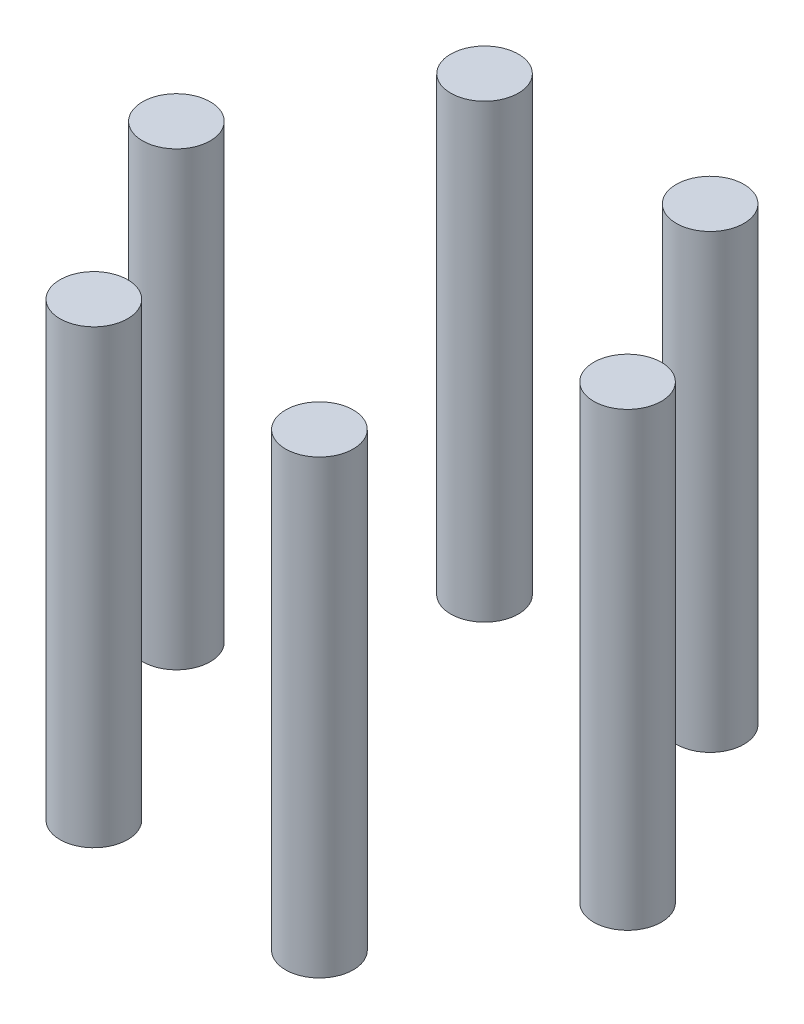
SolidWorks part; units mm, degrees
ref_plane "Front Plane" through (0, 0, 0) normal (0, 0, 1) x (1, 0, 0)
ref_plane "Top Plane" through (0, 0, 0) normal (0, 1, 0) x (1, 0, 0)
ref_plane "Right Plane" through (0, 0, 0) normal (1, 0, 0) x (0, 0, -1)
sketch "Sketch1" plane through (0, 0, 0) normal (0, 1, 0) x (1, 0, 0)
  line L0 (-15.4, 0) -> (14.4, 0) construction
  line L1 (0, 0) -> (0, 14.9128) construction
  line L2 (0, 0) -> (0, -14.9128) construction
  line L3 (0, 0) -> (-0.5, 0) construction
  line L4 (-0.5, 0) -> (-0.5, 15.3103) construction
  line L5 (-0.5, 0) -> (-0.5, -15.3103) construction
  line L6 (14.4, 0) -> (15.5, 0) construction
  line L7 (0, 0) -> (10, 0) construction
  line L8 (7.9, 0) -> (9.5, 0)
  line L9 (-0.5, 0) -> (9.5, 0) construction
  line L10 (-0.5, 15.3103) -> (-0.5, -15.3103) construction
  circle A0 centre (-0.5, 0) radius 16
  circle A1 centre (15.5, 0) radius 1
  circle A2 centre (15.0351, -3.8291) radius 1
  circle A3 centre (13.6673, -7.4356) radius 1
  circle A4 centre (11.4762, -10.61) radius 1
  circle A5 centre (8.589, -13.1677) radius 1
  circle A6 centre (5.1737, -14.9603) radius 1
  circle A7 centre (1.4286, -15.8833) radius 1
  circle A8 centre (-2.4286, -15.8833) radius 1
  circle A9 centre (-6.1737, -14.9603) radius 1
  circle A10 centre (-9.589, -13.1677) radius 1
  circle A11 centre (-12.4762, -10.61) radius 1
  circle A12 centre (-14.6673, -7.4356) radius 1
  circle A13 centre (-16.0351, -3.8291) radius 1
  circle A14 centre (-16.5, 0) radius 1
  circle A15 centre (-16.0351, 3.8291) radius 1
  circle A16 centre (-14.6673, 7.4356) radius 1
  circle A17 centre (-12.4762, 10.61) radius 1
  circle A18 centre (-9.589, 13.1677) radius 1
  circle A19 centre (-6.1737, 14.9603) radius 1
  circle A20 centre (-2.4286, 15.8833) radius 1
  circle A21 centre (1.4286, 15.8833) radius 1
  circle A22 centre (5.1737, 14.9603) radius 1
  circle A23 centre (8.589, 13.1677) radius 1
  circle A24 centre (11.4762, 10.61) radius 1
  circle A25 centre (13.6673, 7.4356) radius 1
  circle A26 centre (15.0351, 3.8291) radius 1
  circle A27 centre (0, 0) radius 10
  circle A28 centre (10, 0) radius 2.1
  circle A29 centre (5, -8.6603) radius 2.1
  circle A30 centre (-5, -8.6603) radius 2.1
  circle A31 centre (-10, 0) radius 2.1
  circle A32 centre (-5, 8.6603) radius 2.1
  circle A33 centre (5, 8.6603) radius 2.1
  circle A34 centre (-6, 8.6603) radius 2.1
  circle A35 centre (4, 8.6603) radius 2.1
  circle A36 centre (9, 0) radius 2.1
  circle A37 centre (4, -8.6603) radius 2.1
  circle A38 centre (-6, -8.6603) radius 2.1
  circle A39 centre (-1, 0) radius 10
  circle A40 centre (-11, 0) radius 2.1
  circle A41 centre (9.5, 0) radius 1.5
  circle A42 centre (4.5, -8.6603) radius 1.5
  circle A43 centre (-5.5, -8.6603) radius 1.5
  circle A44 centre (-10.5, 0) radius 1.5
  circle A45 centre (-5.5, 8.6603) radius 1.5
  circle A46 centre (4.5, 8.6603) radius 1.5
  spline S0 degree 4 poles (14.1521, 3.1658) (14.188, 3.1199) (14.2658, 3.0332) (14.3775, 2.9384) (14.515, 2.8555) (14.6203, 2.806) (14.6874, 2.778) (14.7412, 2.7556) (14.7939, 2.7309) (14.8442, 2.7016) (14.9616, 2.6171) (15.116, 2.4418) (15.2531, 2.163) (15.3044, 1.8261) (15.2781, 1.5454) (15.2134, 1.3341) (15.1457, 1.199) (15.0717, 1.0959) (14.999, 1.0246) (14.9346, 0.9749) (14.8529, 0.9144) (14.7598, 0.8351) (14.6613, 0.7318) (14.5658, 0.5985) (14.4899, 0.4547) (14.4445, 0.3242) (14.4198, 0.2202) (14.4058, 0.1237) (14.3997, 0.036) (14.399, -0.0233) (14.4055, -0.1232) (14.4175, -0.2057) (14.4353, -0.2848) (14.4589, -0.3638) (14.4955, -0.4601) (14.5538, -0.5777) (14.629, -0.6905) (14.7205, -0.7952) (14.8099, -0.8785) (14.886, -0.9397) (14.9653, -0.9969) (15.0394, -1.0608) (15.1018, -1.1365) (15.1543, -1.2193) (15.2086, -1.3292) (15.2563, -1.4688) (15.2881, -1.6381) (15.2945, -1.881) (15.2523, -2.1199) (15.1638, -2.3444) (15.0424, -2.5231) (14.9425, -2.6287) (14.8453, -2.7036) (14.7572, -2.7504) (14.6644, -2.7867) (14.5734, -2.827) (14.4636, -2.8857) (14.309, -2.9902) (14.1305, -3.1658) (13.9721, -3.435) (13.894, -3.7733) (13.9169, -4.0803) (13.9952, -4.3102) (14.0824, -4.4685) (14.1503, -4.5677) (14.21, -4.6429) (14.2706, -4.7176) (14.3202, -4.8002) (14.3654, -4.9109) (14.3993, -5.0496) (14.4169, -5.2624) (14.3843, -5.5009) (14.3041, -5.731) (14.178, -5.9418) (14.0479, -6.0957) (13.9108, -6.2086) (13.7771, -6.2844) (13.6546, -6.3259) (13.5506, -6.3413) (13.4467, -6.3556) (13.3441, -6.3782) (13.2186, -6.4164) (13.0491, -6.4902) (12.8504, -6.6239) (12.6494, -6.8484) (12.5061, -7.1523) (12.463, -7.451) (12.49, -7.6921) (12.5392, -7.8624) (12.5803, -7.968) (12.6183, -8.0504) (12.6544, -8.1336) (12.6783, -8.2214) (12.6929, -8.336) (12.6907, -8.4762) (12.6543, -8.6855) (12.5452, -8.9512) (12.3731, -9.1837) (12.1492, -9.3663) (11.9533, -9.4633) (11.8116, -9.5062) (11.6867, -9.5225) (11.5835, -9.517) (11.4812, -9.5034) (11.3782, -9.4969) (11.2749, -9.4982) (11.1721, -9.508) (11.0085, -9.5382) (10.791, -9.6158) (10.5438, -9.7787) (10.3474, -10.0243) (10.2402, -10.2686) (10.1943, -10.4842) (10.1853, -10.6384) (10.1931, -10.7705) (10.2091, -10.8795) (10.2256, -10.9662) (10.236, -11.0539) (10.2331, -11.1423) (10.2158, -11.2534) (10.1767, -11.3842) (10.0886, -11.5718) (9.9146, -11.8006) (9.6439, -12.0158) (9.3384, -12.1314) (9.0923, -12.1519) (8.9388, -12.1247) (8.8741, -12.1049) (8.8233, -12.0863) (8.76, -12.0622) (8.6577, -12.0268) (8.5127, -11.9913) (8.2954, -11.971) (8.0233, -12.0058) (7.7397, -12.12) (7.4775, -12.3303) (7.3093, -12.5758) (7.2277, -12.7964) (7.1948, -12.9647) (7.1831, -13.0729) (7.1774, -13.16) (7.1639, -13.2682) (7.1207, -13.3961) (7.0432, -13.5357) (6.8963, -13.7154) (6.6678, -13.8963) (6.3478, -14.0387) (6.02, -14.0727) (5.7619, -14.0269) (5.5985, -13.9438) (5.5126, -13.8801) (5.4018, -13.8057) (5.2599, -13.7303) (5.0524, -13.6565) (4.7738, -13.623) (4.4626, -13.6683) (4.1888, -13.7999) (3.9912, -13.9665) (3.8578, -14.1339) (3.7826, -14.2632) (3.7309, -14.3799) (3.6959, -14.48) (3.6689, -14.5606) (3.6251, -14.6573) (3.5494, -14.7647) (3.44, -14.8752) (3.2557, -15.006) (2.9928, -15.1201) (2.6515, -15.1757) (2.3406, -15.1291) (2.1258, -15.0338) (2.011, -14.9468) (1.9698, -14.909) (1.9317, -14.8681) (1.8954, -14.8255) (1.8499, -14.7726) (1.7735, -14.691) (1.6576, -14.5893) (1.4677, -14.4687) (1.2013, -14.3748) (0.8943, -14.3518) (0.5705, -14.4236) (0.3173, -14.5632) (0.1515, -14.7141) (0.0481, -14.8418) (-0.0114, -14.9289) (-0.057, -15) (-0.1205, -15.0845) (-0.2167, -15.1711) (-0.3455, -15.2521) (-0.5484, -15.3356) (-0.8128, -15.3854) (-1.084, -15.3726) (-1.345, -15.2972) (-1.5435, -15.1922) (-1.6658, -15.0976) (-1.7547, -15.002) (-1.8112, -14.9128) (-1.8483, -14.8369) (-1.8948, -14.7422) (-1.9811, -14.5964) (-2.1305, -14.4153) (-2.3717, -14.2374) (-2.6941, -14.1243) (-3.0058, -14.1121) (-3.2798, -14.1742) (-3.4814, -14.2713) (-3.6077, -14.3581) (-3.6929, -14.4296) (-3.7443, -14.4763) (-3.7855, -14.5136) (-3.839, -14.5578) (-3.9718, -14.6426) (-4.2092, -14.7163) (-4.5379, -14.7232) (-4.871, -14.6233) (-5.1192, -14.4741) (-5.2872, -14.3161) (-5.3818, -14.1887) (-5.4416, -14.0686) (-5.4698, -13.9639) (-5.4862, -13.8788) (-5.5106, -13.7734) (-5.5628, -13.6112) (-5.6686, -13.4029) (-5.8615, -13.1808) (-6.1409, -13.0036) (-6.4324, -12.9205) (-6.707, -12.9139) (-6.9246, -12.958) (-7.0705, -13.0119) (-7.1719, -13.0612) (-7.2342, -13.0943) (-7.2842, -13.1203) (-7.3485, -13.1494) (-7.4504, -13.1813) (-7.5929, -13.1993) (-7.8225, -13.1875) (-8.1082, -13.1019) (-8.3607, -12.9481) (-8.5641, -12.7393) (-8.6869, -12.541) (-8.7459, -12.3913) (-8.7711, -12.2579) (-8.7697, -12.1482) (-8.7645, -12.0606) (-8.7633, -11.951) (-8.7731, -11.8212) (-8.8019, -11.6732) (-8.8729, -11.4717) (-9.0045, -11.25) (-9.2205, -11.0351) (-9.4997, -10.8905) (-9.7475, -10.8369) (-9.9383, -10.8322) (-10.0675, -10.8437) (-10.1698, -10.8609) (-10.2704, -10.8859) (-10.3717, -10.9089) (-10.4995, -10.9144) (-10.6499, -10.893) (-10.8644, -10.8236) (-11.1154, -10.6702) (-11.3185, -10.4608) (-11.4614, -10.2119) (-11.5248, -10.0134) (-11.5464, -9.8777) (-11.5487, -9.7646) (-11.5393, -9.6761) (-11.5169, -9.5902) (-11.4896, -9.5058) (-11.4606, -9.3988) (-11.4371, -9.2678) (-11.428, -9.1126) (-11.4489, -8.8917) (-11.5253, -8.6444) (-11.6806, -8.3917) (-11.9083, -8.1893) (-12.1461, -8.0664) (-12.3515, -8.0112) (-12.509, -7.9918) (-12.6408, -7.9895) (-12.7466, -7.9882) (-12.8744, -7.9638) (-13.0178, -7.9059) (-13.1692, -7.8114) (-13.319, -7.6747) (-13.472, -7.4805) (-13.5815, -7.2609) (-13.644, -7.0266) (-13.6529, -6.8129) (-13.6365, -6.6728) (-13.6064, -6.5605) (-13.5704, -6.4764) (-13.5232, -6.3982) (-13.4752, -6.3206) (-13.4215, -6.2199) (-13.3522, -6.0556) (-13.2972, -5.8178) (-13.3061, -5.5112) (-13.4183, -5.1858) (-13.5996, -4.9373) (-13.7884, -4.7826) (-13.9504, -4.6931) (-14.068, -4.6441) (-14.1647, -4.6121) (-14.2634, -4.587) (-14.3606, -4.5562) (-14.4721, -4.4972) (-14.5906, -4.4054) (-14.7415, -4.2409) (-14.8856, -3.984) (-14.9605, -3.7) (-14.9625, -3.4094) (-14.9171, -3.1994) (-14.8649, -3.0655) (-14.8048, -2.9613) (-14.7437, -2.886) (-14.6735, -2.8194) (-14.6048, -2.7515) (-14.5411, -2.6786) (-14.4829, -2.6013) (-14.3984, -2.4684) (-14.3099, -2.2678) (-14.2572, -1.9916) (-14.2948, -1.6527) (-14.4157, -1.3725) (-14.5648, -1.1806) (-14.7009, -1.0585) (-14.8015, -0.9857) (-14.886, -0.9336) (-14.9732, -0.8861) (-15.056, -0.8309) (-15.1453, -0.7457) (-15.2341, -0.6279) (-15.3021, -0.4979) (-15.3506, -0.3595) (-15.3784, -0.2422) (-15.3932, -0.1473) (-15.4005, -0.0379) (-15.4007, 0.0312) (-15.3943, 0.133) (-15.3819, 0.2227) (-15.3632, 0.3082) (-15.3383, 0.3938) (-15.2991, 0.498) (-15.241, 0.614) (-15.1569, 0.7356) (-15.0521, 0.8388) (-14.947, 0.9) (-14.8417, 0.9596) (-14.7374, 1.0292) (-14.6222, 1.1253) (-14.4762, 1.2888) (-14.3483, 1.5104) (-14.2696, 1.788) (-14.2718, 2.0824) (-14.3338, 2.3297) (-14.4228, 2.5131) (-14.5089, 2.6398) (-14.5912, 2.7371) (-14.6628, 2.8095) (-14.7315, 2.8736) (-14.7874, 2.9388) (-14.8392, 3.0187) (-14.9, 3.1445) (-14.933, 3.2628) (-14.9484, 3.3663) (-14.9531, 3.4358) knots 0 0 0 0 0 0.003662 0.007324 0.009155 0.010071 0.010986 0.011902 0.012818 0.013733 0.014649 0.020984 0.02732 0.032959 0.035778 0.038598 0.041156 0.042436 0.043715 0.044995 0.046274 0.048833 0.051398 0.053964 0.05653 0.059096 0.059963 0.060831 0.062566 0.06386 0.065154 0.066448 0.067743 0.069037 0.070331 0.072919 0.075992 0.077529 0.079065 0.080602 0.082139 0.083675 0.085212 0.086754 0.088296 0.09138 0.094464 0.097548 0.103529 0.106519 0.10951 0.111075 0.112641 0.114207 0.115773 0.117339 0.118905 0.122036 0.127492 0.132948 0.138255 0.143562 0.146585 0.148096 0.149608 0.151119 0.15263 0.154142 0.155653 0.158618 0.161583 0.167513 0.170668 0.173824 0.176979 0.180135 0.181785 0.183435 0.185086 0.186736 0.188387 0.190037 0.193338 0.198334 0.203329 0.208757 0.214186 0.217039 0.218465 0.219892 0.221319 0.222745 0.224172 0.225598 0.228568 0.231538 0.237477 0.243509 0.246525 0.249541 0.251164 0.252787 0.25441 0.256033 0.257656 0.259279 0.260902 0.262525 0.268116 0.273708 0.279232 0.281995 0.284757 0.287531 0.288919 0.290306 0.291693 0.293081 0.294468 0.295855 0.298752 0.301648 0.307441 0.313806 0.320171 0.321875 0.322726 0.323578 0.32443 0.325282 0.326985 0.330392 0.333799 0.338942 0.344084 0.349371 0.354658 0.3574 0.358771 0.360142 0.361513 0.362884 0.365627 0.368572 0.371516 0.377406 0.383828 0.390249 0.39193 0.393611 0.395291 0.396972 0.400333 0.403695 0.409076 0.414457 0.419833 0.422521 0.425209 0.427878 0.429213 0.430548 0.431883 0.433218 0.435887 0.438758 0.441629 0.44737 0.453781 0.460191 0.46107 0.46195 0.462829 0.463708 0.464587 0.465466 0.467225 0.470742 0.474259 0.479542 0.484825 0.489836 0.494847 0.497504 0.498832 0.500161 0.501489 0.502818 0.505475 0.508247 0.51102 0.516564 0.52227 0.525123 0.527976 0.530631 0.531959 0.533286 0.534614 0.535941 0.538597 0.543936 0.549276 0.554531 0.559787 0.563284 0.566782 0.568531 0.569405 0.570279 0.571154 0.572028 0.573777 0.580153 0.586529 0.592383 0.595311 0.598238 0.600963 0.602326 0.603688 0.605051 0.606414 0.609139 0.614393 0.619646 0.62466 0.629675 0.633224 0.636772 0.638547 0.639434 0.640321 0.641208 0.642095 0.64387 0.647026 0.650182 0.656494 0.66242 0.665383 0.668345 0.671105 0.672484 0.673864 0.675243 0.676623 0.679382 0.682041 0.684701 0.690021 0.695473 0.700926 0.704188 0.705819 0.70745 0.709081 0.710712 0.712344 0.713975 0.717095 0.720216 0.726458 0.732287 0.735201 0.738116 0.739511 0.740907 0.742302 0.743698 0.745093 0.746488 0.749279 0.752059 0.754839 0.760398 0.765424 0.770449 0.773769 0.777088 0.778748 0.780408 0.782068 0.783727 0.786901 0.790075 0.793249 0.796422 0.802397 0.805385 0.808372 0.809808 0.811244 0.812679 0.814115 0.81555 0.816986 0.819857 0.825318 0.830779 0.83599 0.841201 0.844404 0.846006 0.847607 0.849209 0.850811 0.852412 0.854014 0.857107 0.8602 0.866387 0.872353 0.875336 0.878319 0.87984 0.881361 0.882882 0.884402 0.885923 0.887444 0.888965 0.890486 0.895823 0.90116 0.906397 0.911634 0.914757 0.916319 0.91788 0.919441 0.921003 0.922564 0.924126 0.927182 0.930238 0.931767 0.933295 0.934823 0.936351 0.937751 0.93915 0.940549 0.941949 0.943348 0.944747 0.947546 0.950087 0.952628 0.953898 0.955168 0.957709 0.960509 0.96331 0.96891 0.973663 0.978415 0.981621 0.984826 0.986428 0.988031 0.989634 0.991236 0.992332 0.993427 0.995618 1 1 1 1 1 construction
  spline S1 degree 4 poles (14.4, 0) (14.4, -0.018) (14.401, -0.0542) (14.4055, -0.1232) (14.4175, -0.2057) (14.4353, -0.2848) (14.4589, -0.3638) (14.4955, -0.4601) (14.5538, -0.5777) (14.629, -0.6905) (14.7205, -0.7952) (14.8099, -0.8785) (14.886, -0.9397) (14.9653, -0.9969) (15.0394, -1.0608) (15.1018, -1.1365) (15.1543, -1.2193) (15.2086, -1.3292) (15.2563, -1.4688) (15.2881, -1.6381) (15.2945, -1.881) (15.2523, -2.1199) (15.1638, -2.3444) (15.0424, -2.5231) (14.9425, -2.6287) (14.8453, -2.7036) (14.7572, -2.7504) (14.6644, -2.7867) (14.5734, -2.827) (14.4636, -2.8857) (14.309, -2.9902) (14.1305, -3.1658) (13.9721, -3.435) (13.894, -3.7733) (13.9169, -4.0803) (13.9952, -4.3102) (14.0824, -4.4685) (14.1503, -4.5677) (14.21, -4.6429) (14.2706, -4.7176) (14.3202, -4.8002) (14.3654, -4.9109) (14.3993, -5.0496) (14.4169, -5.2624) (14.3843, -5.5009) (14.3041, -5.731) (14.178, -5.9418) (14.0479, -6.0957) (13.9108, -6.2086) (13.7771, -6.2844) (13.6546, -6.3259) (13.5506, -6.3413) (13.4467, -6.3556) (13.3441, -6.3782) (13.2186, -6.4164) (13.0491, -6.4902) (12.8504, -6.6239) (12.6494, -6.8484) (12.5061, -7.1523) (12.463, -7.451) (12.49, -7.6921) (12.5392, -7.8624) (12.5803, -7.968) (12.6183, -8.0504) (12.6544, -8.1336) (12.6783, -8.2214) (12.6929, -8.336) (12.6907, -8.4762) (12.6543, -8.6855) (12.5452, -8.9512) (12.3731, -9.1837) (12.1492, -9.3663) (11.9533, -9.4633) (11.8116, -9.5062) (11.6867, -9.5225) (11.5835, -9.517) (11.4812, -9.5034) (11.3782, -9.4969) (11.2749, -9.4982) (11.1721, -9.508) (11.0085, -9.5382) (10.791, -9.6158) (10.5438, -9.7787) (10.3474, -10.0243) (10.2402, -10.2686) (10.1943, -10.4842) (10.1853, -10.6384) (10.1931, -10.7705) (10.2091, -10.8795) (10.2256, -10.9662) (10.236, -11.0539) (10.2331, -11.1423) (10.2158, -11.2534) (10.1767, -11.3842) (10.0886, -11.5718) (9.9146, -11.8006) (9.6439, -12.0158) (9.3384, -12.1314) (9.0923, -12.1519) (8.9388, -12.1247) (8.8741, -12.1049) (8.8233, -12.0863) (8.76, -12.0622) (8.6577, -12.0268) (8.5127, -11.9913) (8.2954, -11.971) (8.0233, -12.0058) (7.7397, -12.12) (7.4775, -12.3303) (7.3093, -12.5758) (7.2277, -12.7964) (7.1948, -12.9647) (7.1831, -13.0729) (7.1774, -13.16) (7.1639, -13.2682) (7.1207, -13.3961) (7.0432, -13.5357) (6.8963, -13.7154) (6.6678, -13.8963) (6.3478, -14.0387) (6.02, -14.0727) (5.7619, -14.0269) (5.5985, -13.9438) (5.5126, -13.8801) (5.4018, -13.8057) (5.2599, -13.7303) (5.0524, -13.6565) (4.7738, -13.623) (4.4626, -13.6683) (4.1888, -13.7999) (3.9912, -13.9665) (3.8578, -14.1339) (3.7826, -14.2632) (3.7309, -14.3799) (3.6959, -14.48) (3.6689, -14.5606) (3.6251, -14.6573) (3.5494, -14.7647) (3.44, -14.8752) (3.2557, -15.006) (2.9928, -15.1201) (2.6515, -15.1757) (2.3406, -15.1291) (2.1258, -15.0338) (2.011, -14.9468) (1.9698, -14.909) (1.9317, -14.8681) (1.8954, -14.8255) (1.8499, -14.7726) (1.7735, -14.691) (1.6576, -14.5893) (1.4677, -14.4687) (1.2013, -14.3748) (0.8943, -14.3518) (0.5705, -14.4236) (0.3173, -14.5632) (0.1515, -14.7141) (0.0481, -14.8418) (-0.0114, -14.9289) (-0.057, -15) (-0.1205, -15.0845) (-0.2167, -15.1711) (-0.3455, -15.2521) (-0.5484, -15.3356) (-0.8128, -15.3854) (-1.084, -15.3726) (-1.345, -15.2972) (-1.5435, -15.1922) (-1.6658, -15.0976) (-1.7547, -15.002) (-1.8112, -14.9128) (-1.8483, -14.8369) (-1.8948, -14.7422) (-1.9811, -14.5964) (-2.1305, -14.4153) (-2.3717, -14.2374) (-2.6941, -14.1243) (-3.0058, -14.1121) (-3.2798, -14.1742) (-3.4814, -14.2713) (-3.6077, -14.3581) (-3.6929, -14.4296) (-3.7443, -14.4763) (-3.7855, -14.5136) (-3.839, -14.5578) (-3.9718, -14.6426) (-4.2092, -14.7163) (-4.5379, -14.7232) (-4.871, -14.6233) (-5.1192, -14.4741) (-5.2872, -14.3161) (-5.3818, -14.1887) (-5.4416, -14.0686) (-5.4698, -13.9639) (-5.4862, -13.8788) (-5.5106, -13.7734) (-5.5628, -13.6112) (-5.6686, -13.4029) (-5.8615, -13.1808) (-6.1409, -13.0036) (-6.4324, -12.9205) (-6.707, -12.9139) (-6.9246, -12.958) (-7.0705, -13.0119) (-7.1719, -13.0612) (-7.2342, -13.0943) (-7.2842, -13.1203) (-7.3485, -13.1494) (-7.4504, -13.1813) (-7.5929, -13.1993) (-7.8225, -13.1875) (-8.1082, -13.1019) (-8.3607, -12.9481) (-8.5641, -12.7393) (-8.6869, -12.541) (-8.7459, -12.3913) (-8.7711, -12.2579) (-8.7697, -12.1482) (-8.7645, -12.0606) (-8.7633, -11.951) (-8.7731, -11.8212) (-8.8019, -11.6732) (-8.8729, -11.4717) (-9.0045, -11.25) (-9.2205, -11.0351) (-9.4997, -10.8905) (-9.7475, -10.8369) (-9.9383, -10.8322) (-10.0675, -10.8437) (-10.1698, -10.8609) (-10.2704, -10.8859) (-10.3717, -10.9089) (-10.4995, -10.9144) (-10.6499, -10.893) (-10.8644, -10.8236) (-11.1154, -10.6702) (-11.3185, -10.4608) (-11.4614, -10.2119) (-11.5248, -10.0134) (-11.5464, -9.8777) (-11.5487, -9.7646) (-11.5393, -9.6761) (-11.5169, -9.5902) (-11.4896, -9.5058) (-11.4606, -9.3988) (-11.4371, -9.2678) (-11.428, -9.1126) (-11.4489, -8.8917) (-11.5253, -8.6444) (-11.6806, -8.3917) (-11.9083, -8.1893) (-12.1461, -8.0664) (-12.3515, -8.0112) (-12.509, -7.9918) (-12.6408, -7.9895) (-12.7466, -7.9882) (-12.8744, -7.9638) (-13.0178, -7.9059) (-13.1692, -7.8114) (-13.319, -7.6747) (-13.472, -7.4805) (-13.5815, -7.2609) (-13.644, -7.0266) (-13.6529, -6.8129) (-13.6365, -6.6728) (-13.6064, -6.5605) (-13.5704, -6.4764) (-13.5232, -6.3982) (-13.4752, -6.3206) (-13.4215, -6.2199) (-13.3522, -6.0556) (-13.2972, -5.8178) (-13.3061, -5.5112) (-13.4183, -5.1858) (-13.5996, -4.9373) (-13.7884, -4.7826) (-13.9504, -4.6931) (-14.068, -4.6441) (-14.1647, -4.6121) (-14.2634, -4.587) (-14.3606, -4.5562) (-14.4721, -4.4972) (-14.5906, -4.4054) (-14.7415, -4.2409) (-14.8856, -3.984) (-14.9605, -3.7) (-14.9625, -3.4094) (-14.9171, -3.1994) (-14.8649, -3.0655) (-14.8048, -2.9613) (-14.7437, -2.886) (-14.6735, -2.8194) (-14.6048, -2.7515) (-14.5411, -2.6786) (-14.4829, -2.6013) (-14.3984, -2.4684) (-14.3099, -2.2678) (-14.2572, -1.9916) (-14.2948, -1.6527) (-14.4157, -1.3725) (-14.5648, -1.1806) (-14.7009, -1.0585) (-14.8015, -0.9857) (-14.886, -0.9336) (-14.9732, -0.8861) (-15.056, -0.8309) (-15.1453, -0.7457) (-15.2341, -0.6279) (-15.3021, -0.4979) (-15.3506, -0.3595) (-15.3784, -0.2422) (-15.3932, -0.1473) (-15.3988, -0.0635) (-15.4, -0.0212) (-15.4, 0) knots 0.062566 0.062566 0.062566 0.062566 0.062566 0.06386 0.065154 0.066448 0.067743 0.069037 0.070331 0.072919 0.075992 0.077529 0.079065 0.080602 0.082139 0.083675 0.085212 0.086754 0.088296 0.09138 0.094464 0.097548 0.103529 0.106519 0.10951 0.111075 0.112641 0.114207 0.115773 0.117339 0.118905 0.122036 0.127492 0.132948 0.138255 0.143562 0.146585 0.148096 0.149608 0.151119 0.15263 0.154142 0.155653 0.158618 0.161583 0.167513 0.170668 0.173824 0.176979 0.180135 0.181785 0.183435 0.185086 0.186736 0.188387 0.190037 0.193338 0.198334 0.203329 0.208757 0.214186 0.217039 0.218465 0.219892 0.221319 0.222745 0.224172 0.225598 0.228568 0.231538 0.237477 0.243509 0.246525 0.249541 0.251164 0.252787 0.25441 0.256033 0.257656 0.259279 0.260902 0.262525 0.268116 0.273708 0.279232 0.281995 0.284757 0.287531 0.288919 0.290306 0.291693 0.293081 0.294468 0.295855 0.298752 0.301648 0.307441 0.313806 0.320171 0.321875 0.322726 0.323578 0.32443 0.325282 0.326985 0.330392 0.333799 0.338942 0.344084 0.349371 0.354658 0.3574 0.358771 0.360142 0.361513 0.362884 0.365627 0.368572 0.371516 0.377406 0.383828 0.390249 0.39193 0.393611 0.395291 0.396972 0.400333 0.403695 0.409076 0.414457 0.419833 0.422521 0.425209 0.427878 0.429213 0.430548 0.431883 0.433218 0.435887 0.438758 0.441629 0.44737 0.453781 0.460191 0.46107 0.46195 0.462829 0.463708 0.464587 0.465466 0.467225 0.470742 0.474259 0.479542 0.484825 0.489836 0.494847 0.497504 0.498832 0.500161 0.501489 0.502818 0.505475 0.508247 0.51102 0.516564 0.52227 0.525123 0.527976 0.530631 0.531959 0.533286 0.534614 0.535941 0.538597 0.543936 0.549276 0.554531 0.559787 0.563284 0.566782 0.568531 0.569405 0.570279 0.571154 0.572028 0.573777 0.580153 0.586529 0.592383 0.595311 0.598238 0.600963 0.602326 0.603688 0.605051 0.606414 0.609139 0.614393 0.619646 0.62466 0.629675 0.633224 0.636772 0.638547 0.639434 0.640321 0.641208 0.642095 0.64387 0.647026 0.650182 0.656494 0.66242 0.665383 0.668345 0.671105 0.672484 0.673864 0.675243 0.676623 0.679382 0.682041 0.684701 0.690021 0.695473 0.700926 0.704188 0.705819 0.70745 0.709081 0.710712 0.712344 0.713975 0.717095 0.720216 0.726458 0.732287 0.735201 0.738116 0.739511 0.740907 0.742302 0.743698 0.745093 0.746488 0.749279 0.752059 0.754839 0.760398 0.765424 0.770449 0.773769 0.777088 0.778748 0.780408 0.782068 0.783727 0.786901 0.790075 0.793249 0.796422 0.802397 0.805385 0.808372 0.809808 0.811244 0.812679 0.814115 0.81555 0.816986 0.819857 0.825318 0.830779 0.83599 0.841201 0.844404 0.846006 0.847607 0.849209 0.850811 0.852412 0.854014 0.857107 0.8602 0.866387 0.872353 0.875336 0.878319 0.87984 0.881361 0.882882 0.884402 0.885923 0.887444 0.888965 0.890486 0.895823 0.90116 0.906397 0.911634 0.914757 0.916319 0.91788 0.919441 0.921003 0.922564 0.924126 0.927182 0.930238 0.931767 0.933295 0.934823 0.936351 0.936351 0.936351 0.936351 0.936351
  spline S2 degree 4 poles (14.4, 0) (14.4, 0.018) (14.401, 0.0542) (14.4055, 0.1232) (14.4175, 0.2057) (14.4353, 0.2848) (14.4589, 0.3638) (14.4955, 0.4601) (14.5538, 0.5777) (14.629, 0.6905) (14.7205, 0.7952) (14.8099, 0.8785) (14.886, 0.9397) (14.9653, 0.9969) (15.0394, 1.0608) (15.1018, 1.1365) (15.1543, 1.2193) (15.2086, 1.3292) (15.2563, 1.4688) (15.2881, 1.6381) (15.2945, 1.881) (15.2523, 2.1199) (15.1638, 2.3444) (15.0424, 2.5231) (14.9425, 2.6287) (14.8453, 2.7036) (14.7572, 2.7504) (14.6644, 2.7867) (14.5734, 2.827) (14.4636, 2.8857) (14.309, 2.9902) (14.1305, 3.1658) (13.9721, 3.435) (13.894, 3.7733) (13.9169, 4.0803) (13.9952, 4.3102) (14.0824, 4.4685) (14.1503, 4.5677) (14.21, 4.6429) (14.2706, 4.7176) (14.3202, 4.8002) (14.3654, 4.9109) (14.3993, 5.0496) (14.4169, 5.2624) (14.3843, 5.5009) (14.3041, 5.731) (14.178, 5.9418) (14.0479, 6.0957) (13.9108, 6.2086) (13.7771, 6.2844) (13.6546, 6.3259) (13.5506, 6.3413) (13.4467, 6.3556) (13.3441, 6.3782) (13.2186, 6.4164) (13.0491, 6.4902) (12.8504, 6.6239) (12.6494, 6.8484) (12.5061, 7.1523) (12.463, 7.451) (12.49, 7.6921) (12.5392, 7.8624) (12.5803, 7.968) (12.6183, 8.0504) (12.6544, 8.1336) (12.6783, 8.2214) (12.6929, 8.336) (12.6907, 8.4762) (12.6543, 8.6855) (12.5452, 8.9512) (12.3731, 9.1837) (12.1492, 9.3663) (11.9533, 9.4633) (11.8116, 9.5062) (11.6867, 9.5225) (11.5835, 9.517) (11.4812, 9.5034) (11.3782, 9.4969) (11.2749, 9.4982) (11.1721, 9.508) (11.0085, 9.5382) (10.791, 9.6158) (10.5438, 9.7787) (10.3474, 10.0243) (10.2402, 10.2686) (10.1943, 10.4842) (10.1853, 10.6384) (10.1931, 10.7705) (10.2091, 10.8795) (10.2256, 10.9662) (10.236, 11.0539) (10.2331, 11.1423) (10.2158, 11.2534) (10.1767, 11.3842) (10.0886, 11.5718) (9.9146, 11.8006) (9.6439, 12.0158) (9.3384, 12.1314) (9.0923, 12.1519) (8.9388, 12.1247) (8.8741, 12.1049) (8.8233, 12.0863) (8.76, 12.0622) (8.6577, 12.0268) (8.5127, 11.9913) (8.2954, 11.971) (8.0233, 12.0058) (7.7397, 12.12) (7.4775, 12.3303) (7.3093, 12.5758) (7.2277, 12.7964) (7.1948, 12.9647) (7.1831, 13.0729) (7.1774, 13.16) (7.1639, 13.2682) (7.1207, 13.3961) (7.0432, 13.5357) (6.8963, 13.7154) (6.6678, 13.8963) (6.3478, 14.0387) (6.02, 14.0727) (5.7619, 14.0269) (5.5985, 13.9438) (5.5126, 13.8801) (5.4018, 13.8057) (5.2599, 13.7303) (5.0524, 13.6565) (4.7738, 13.623) (4.4626, 13.6683) (4.1888, 13.7999) (3.9912, 13.9665) (3.8578, 14.1339) (3.7826, 14.2632) (3.7309, 14.3799) (3.6959, 14.48) (3.6689, 14.5606) (3.6251, 14.6573) (3.5494, 14.7647) (3.44, 14.8752) (3.2557, 15.006) (2.9928, 15.1201) (2.6515, 15.1757) (2.3406, 15.1291) (2.1258, 15.0338) (2.011, 14.9468) (1.9698, 14.909) (1.9317, 14.8681) (1.8954, 14.8255) (1.8499, 14.7726) (1.7735, 14.691) (1.6576, 14.5893) (1.4677, 14.4687) (1.2013, 14.3748) (0.8943, 14.3518) (0.5705, 14.4236) (0.3173, 14.5632) (0.1515, 14.7141) (0.0481, 14.8418) (-0.0114, 14.9289) (-0.057, 15) (-0.1205, 15.0845) (-0.2167, 15.1711) (-0.3455, 15.2521) (-0.5484, 15.3356) (-0.8128, 15.3854) (-1.084, 15.3726) (-1.345, 15.2972) (-1.5435, 15.1922) (-1.6658, 15.0976) (-1.7547, 15.002) (-1.8112, 14.9128) (-1.8483, 14.8369) (-1.8948, 14.7422) (-1.9811, 14.5964) (-2.1305, 14.4153) (-2.3717, 14.2374) (-2.6941, 14.1243) (-3.0058, 14.1121) (-3.2798, 14.1742) (-3.4814, 14.2713) (-3.6077, 14.3581) (-3.6929, 14.4296) (-3.7443, 14.4763) (-3.7855, 14.5136) (-3.839, 14.5578) (-3.9718, 14.6426) (-4.2092, 14.7163) (-4.5379, 14.7232) (-4.871, 14.6233) (-5.1192, 14.4741) (-5.2872, 14.3161) (-5.3818, 14.1887) (-5.4416, 14.0686) (-5.4698, 13.9639) (-5.4862, 13.8788) (-5.5106, 13.7734) (-5.5628, 13.6112) (-5.6686, 13.4029) (-5.8615, 13.1808) (-6.1409, 13.0036) (-6.4324, 12.9205) (-6.707, 12.9139) (-6.9246, 12.958) (-7.0705, 13.0119) (-7.1719, 13.0612) (-7.2342, 13.0943) (-7.2842, 13.1203) (-7.3485, 13.1494) (-7.4504, 13.1813) (-7.5929, 13.1993) (-7.8225, 13.1875) (-8.1082, 13.1019) (-8.3607, 12.9481) (-8.5641, 12.7393) (-8.6869, 12.541) (-8.7459, 12.3913) (-8.7711, 12.2579) (-8.7697, 12.1482) (-8.7645, 12.0606) (-8.7633, 11.951) (-8.7731, 11.8212) (-8.8019, 11.6732) (-8.8729, 11.4717) (-9.0045, 11.25) (-9.2205, 11.0351) (-9.4997, 10.8905) (-9.7475, 10.8369) (-9.9383, 10.8322) (-10.0675, 10.8437) (-10.1698, 10.8609) (-10.2704, 10.8859) (-10.3717, 10.9089) (-10.4995, 10.9144) (-10.6499, 10.893) (-10.8644, 10.8236) (-11.1154, 10.6702) (-11.3185, 10.4608) (-11.4614, 10.2119) (-11.5248, 10.0134) (-11.5464, 9.8777) (-11.5487, 9.7646) (-11.5393, 9.6761) (-11.5169, 9.5902) (-11.4896, 9.5058) (-11.4606, 9.3988) (-11.4371, 9.2678) (-11.428, 9.1126) (-11.4489, 8.8917) (-11.5253, 8.6444) (-11.6806, 8.3917) (-11.9083, 8.1893) (-12.1461, 8.0664) (-12.3515, 8.0112) (-12.509, 7.9918) (-12.6408, 7.9895) (-12.7466, 7.9882) (-12.8744, 7.9638) (-13.0178, 7.9059) (-13.1692, 7.8114) (-13.319, 7.6747) (-13.472, 7.4805) (-13.5815, 7.2609) (-13.644, 7.0266) (-13.6529, 6.8129) (-13.6365, 6.6728) (-13.6064, 6.5605) (-13.5704, 6.4764) (-13.5232, 6.3982) (-13.4752, 6.3206) (-13.4215, 6.2199) (-13.3522, 6.0556) (-13.2972, 5.8178) (-13.3061, 5.5112) (-13.4183, 5.1858) (-13.5996, 4.9373) (-13.7884, 4.7826) (-13.9504, 4.6931) (-14.068, 4.6441) (-14.1647, 4.6121) (-14.2634, 4.587) (-14.3606, 4.5562) (-14.4721, 4.4972) (-14.5906, 4.4054) (-14.7415, 4.2409) (-14.8856, 3.984) (-14.9605, 3.7) (-14.9625, 3.4094) (-14.9171, 3.1994) (-14.8649, 3.0655) (-14.8048, 2.9613) (-14.7437, 2.886) (-14.6735, 2.8194) (-14.6048, 2.7515) (-14.5411, 2.6786) (-14.4829, 2.6013) (-14.3984, 2.4684) (-14.3099, 2.2678) (-14.2572, 1.9916) (-14.2948, 1.6527) (-14.4157, 1.3725) (-14.5648, 1.1806) (-14.7009, 1.0585) (-14.8015, 0.9857) (-14.886, 0.9336) (-14.9732, 0.8861) (-15.056, 0.8309) (-15.1453, 0.7457) (-15.2341, 0.6279) (-15.3021, 0.4979) (-15.3506, 0.3595) (-15.3784, 0.2422) (-15.3932, 0.1473) (-15.3988, 0.0635) (-15.4, 0.0212) (-15.4, 0) knots 0.062566 0.062566 0.062566 0.062566 0.062566 0.06386 0.065154 0.066448 0.067743 0.069037 0.070331 0.072919 0.075992 0.077529 0.079065 0.080602 0.082139 0.083675 0.085212 0.086754 0.088296 0.09138 0.094464 0.097548 0.103529 0.106519 0.10951 0.111075 0.112641 0.114207 0.115773 0.117339 0.118905 0.122036 0.127492 0.132948 0.138255 0.143562 0.146585 0.148096 0.149608 0.151119 0.15263 0.154142 0.155653 0.158618 0.161583 0.167513 0.170668 0.173824 0.176979 0.180135 0.181785 0.183435 0.185086 0.186736 0.188387 0.190037 0.193338 0.198334 0.203329 0.208757 0.214186 0.217039 0.218465 0.219892 0.221319 0.222745 0.224172 0.225598 0.228568 0.231538 0.237477 0.243509 0.246525 0.249541 0.251164 0.252787 0.25441 0.256033 0.257656 0.259279 0.260902 0.262525 0.268116 0.273708 0.279232 0.281995 0.284757 0.287531 0.288919 0.290306 0.291693 0.293081 0.294468 0.295855 0.298752 0.301648 0.307441 0.313806 0.320171 0.321875 0.322726 0.323578 0.32443 0.325282 0.326985 0.330392 0.333799 0.338942 0.344084 0.349371 0.354658 0.3574 0.358771 0.360142 0.361513 0.362884 0.365627 0.368572 0.371516 0.377406 0.383828 0.390249 0.39193 0.393611 0.395291 0.396972 0.400333 0.403695 0.409076 0.414457 0.419833 0.422521 0.425209 0.427878 0.429213 0.430548 0.431883 0.433218 0.435887 0.438758 0.441629 0.44737 0.453781 0.460191 0.46107 0.46195 0.462829 0.463708 0.464587 0.465466 0.467225 0.470742 0.474259 0.479542 0.484825 0.489836 0.494847 0.497504 0.498832 0.500161 0.501489 0.502818 0.505475 0.508247 0.51102 0.516564 0.52227 0.525123 0.527976 0.530631 0.531959 0.533286 0.534614 0.535941 0.538597 0.543936 0.549276 0.554531 0.559787 0.563284 0.566782 0.568531 0.569405 0.570279 0.571154 0.572028 0.573777 0.580153 0.586529 0.592383 0.595311 0.598238 0.600963 0.602326 0.603688 0.605051 0.606414 0.609139 0.614393 0.619646 0.62466 0.629675 0.633224 0.636772 0.638547 0.639434 0.640321 0.641208 0.642095 0.64387 0.647026 0.650182 0.656494 0.66242 0.665383 0.668345 0.671105 0.672484 0.673864 0.675243 0.676623 0.679382 0.682041 0.684701 0.690021 0.695473 0.700926 0.704188 0.705819 0.70745 0.709081 0.710712 0.712344 0.713975 0.717095 0.720216 0.726458 0.732287 0.735201 0.738116 0.739511 0.740907 0.742302 0.743698 0.745093 0.746488 0.749279 0.752059 0.754839 0.760398 0.765424 0.770449 0.773769 0.777088 0.778748 0.780408 0.782068 0.783727 0.786901 0.790075 0.793249 0.796422 0.802397 0.805385 0.808372 0.809808 0.811244 0.812679 0.814115 0.81555 0.816986 0.819857 0.825318 0.830779 0.83599 0.841201 0.844404 0.846006 0.847607 0.849209 0.850811 0.852412 0.854014 0.857107 0.8602 0.866387 0.872353 0.875336 0.878319 0.87984 0.881361 0.882882 0.884402 0.885923 0.887444 0.888965 0.890486 0.895823 0.90116 0.906397 0.911634 0.914757 0.916319 0.91788 0.919441 0.921003 0.922564 0.924126 0.927182 0.930238 0.931767 0.933295 0.934823 0.936351 0.936351 0.936351 0.936351 0.936351
  spline S3 degree 4 poles (-15.4, 0) (-15.4, 0.018) (-15.401, 0.0542) (-15.4055, 0.1232) (-15.4175, 0.2057) (-15.4353, 0.2848) (-15.4589, 0.3638) (-15.4955, 0.4601) (-15.5538, 0.5777) (-15.629, 0.6905) (-15.7205, 0.7952) (-15.8099, 0.8785) (-15.886, 0.9397) (-15.9653, 0.9969) (-16.0394, 1.0608) (-16.1018, 1.1365) (-16.1543, 1.2193) (-16.2086, 1.3292) (-16.2563, 1.4688) (-16.2881, 1.6381) (-16.2945, 1.881) (-16.2523, 2.1199) (-16.1638, 2.3444) (-16.0424, 2.5231) (-15.9425, 2.6287) (-15.8453, 2.7036) (-15.7572, 2.7504) (-15.6644, 2.7867) (-15.5734, 2.827) (-15.4636, 2.8857) (-15.309, 2.9902) (-15.1305, 3.1658) (-14.9721, 3.435) (-14.894, 3.7733) (-14.9169, 4.0803) (-14.9952, 4.3102) (-15.0824, 4.4685) (-15.1503, 4.5677) (-15.21, 4.6429) (-15.2706, 4.7176) (-15.3202, 4.8002) (-15.3654, 4.9109) (-15.3993, 5.0496) (-15.4169, 5.2624) (-15.3843, 5.5009) (-15.3041, 5.731) (-15.178, 5.9418) (-15.0479, 6.0957) (-14.9108, 6.2086) (-14.7771, 6.2844) (-14.6546, 6.3259) (-14.5506, 6.3413) (-14.4467, 6.3556) (-14.3441, 6.3782) (-14.2186, 6.4164) (-14.0491, 6.4902) (-13.8504, 6.6239) (-13.6494, 6.8484) (-13.5061, 7.1523) (-13.463, 7.451) (-13.49, 7.6921) (-13.5392, 7.8624) (-13.5803, 7.968) (-13.6183, 8.0504) (-13.6544, 8.1336) (-13.6783, 8.2214) (-13.6929, 8.336) (-13.6907, 8.4762) (-13.6543, 8.6855) (-13.5452, 8.9512) (-13.3731, 9.1837) (-13.1492, 9.3663) (-12.9533, 9.4633) (-12.8116, 9.5062) (-12.6867, 9.5225) (-12.5835, 9.517) (-12.4812, 9.5034) (-12.3782, 9.4969) (-12.2749, 9.4982) (-12.1721, 9.508) (-12.0085, 9.5382) (-11.791, 9.6158) (-11.5438, 9.7787) (-11.3474, 10.0243) (-11.2402, 10.2686) (-11.1943, 10.4842) (-11.1853, 10.6384) (-11.1931, 10.7705) (-11.2091, 10.8795) (-11.2256, 10.9662) (-11.236, 11.0539) (-11.2331, 11.1423) (-11.2158, 11.2534) (-11.1767, 11.3842) (-11.0886, 11.5718) (-10.9146, 11.8006) (-10.6439, 12.0158) (-10.3384, 12.1314) (-10.0923, 12.1519) (-9.9388, 12.1247) (-9.8741, 12.1049) (-9.8233, 12.0863) (-9.76, 12.0622) (-9.6577, 12.0268) (-9.5127, 11.9913) (-9.2954, 11.971) (-9.0233, 12.0058) (-8.7397, 12.12) (-8.4775, 12.3303) (-8.3093, 12.5758) (-8.2277, 12.7964) (-8.1948, 12.9647) (-8.1831, 13.0729) (-8.1774, 13.16) (-8.1639, 13.2682) (-8.1207, 13.3961) (-8.0432, 13.5357) (-7.8963, 13.7154) (-7.6678, 13.8963) (-7.3478, 14.0387) (-7.02, 14.0727) (-6.7619, 14.0269) (-6.5985, 13.9438) (-6.5126, 13.8801) (-6.4018, 13.8057) (-6.2599, 13.7303) (-6.0524, 13.6565) (-5.7738, 13.623) (-5.4626, 13.6683) (-5.1888, 13.7999) (-4.9912, 13.9665) (-4.8578, 14.1339) (-4.7826, 14.2632) (-4.7309, 14.3799) (-4.6959, 14.48) (-4.6689, 14.5606) (-4.6251, 14.6573) (-4.5494, 14.7647) (-4.44, 14.8752) (-4.2557, 15.006) (-3.9928, 15.1201) (-3.6515, 15.1757) (-3.3406, 15.1291) (-3.1258, 15.0338) (-3.011, 14.9468) (-2.9698, 14.909) (-2.9317, 14.8681) (-2.8954, 14.8255) (-2.8499, 14.7726) (-2.7735, 14.691) (-2.6576, 14.5893) (-2.4677, 14.4687) (-2.2013, 14.3748) (-1.8943, 14.3518) (-1.5705, 14.4236) (-1.3173, 14.5632) (-1.1515, 14.7141) (-1.0481, 14.8418) (-0.9886, 14.9289) (-0.943, 15) (-0.8795, 15.0845) (-0.7833, 15.1711) (-0.6545, 15.2521) (-0.4516, 15.3356) (-0.1872, 15.3854) (0.084, 15.3726) (0.345, 15.2972) (0.5435, 15.1922) (0.6658, 15.0976) (0.7547, 15.002) (0.8112, 14.9128) (0.8483, 14.8369) (0.8948, 14.7422) (0.9811, 14.5964) (1.1305, 14.4153) (1.3717, 14.2374) (1.6941, 14.1243) (2.0058, 14.1121) (2.2798, 14.1742) (2.4814, 14.2713) (2.6077, 14.3581) (2.6929, 14.4296) (2.7443, 14.4763) (2.7855, 14.5136) (2.839, 14.5578) (2.9718, 14.6426) (3.2092, 14.7163) (3.5379, 14.7232) (3.871, 14.6233) (4.1192, 14.4741) (4.2872, 14.3161) (4.3818, 14.1887) (4.4416, 14.0686) (4.4698, 13.9639) (4.4862, 13.8788) (4.5106, 13.7734) (4.5628, 13.6112) (4.6686, 13.4029) (4.8615, 13.1808) (5.1409, 13.0036) (5.4324, 12.9205) (5.707, 12.9139) (5.9246, 12.958) (6.0705, 13.0119) (6.1719, 13.0612) (6.2342, 13.0943) (6.2842, 13.1203) (6.3485, 13.1494) (6.4504, 13.1813) (6.5929, 13.1993) (6.8225, 13.1875) (7.1082, 13.1019) (7.3607, 12.9481) (7.5641, 12.7393) (7.6869, 12.541) (7.7459, 12.3913) (7.7711, 12.2579) (7.7697, 12.1482) (7.7645, 12.0606) (7.7633, 11.951) (7.7731, 11.8212) (7.8019, 11.6732) (7.8729, 11.4717) (8.0045, 11.25) (8.2205, 11.0351) (8.4997, 10.8905) (8.7475, 10.8369) (8.9383, 10.8322) (9.0675, 10.8437) (9.1698, 10.8609) (9.2704, 10.8859) (9.3717, 10.9089) (9.4995, 10.9144) (9.6499, 10.893) (9.8644, 10.8236) (10.1154, 10.6702) (10.3185, 10.4608) (10.4614, 10.2119) (10.5248, 10.0134) (10.5464, 9.8777) (10.5487, 9.7646) (10.5393, 9.6761) (10.5169, 9.5902) (10.4896, 9.5058) (10.4606, 9.3988) (10.4371, 9.2678) (10.428, 9.1126) (10.4489, 8.8917) (10.5253, 8.6444) (10.6806, 8.3917) (10.9083, 8.1893) (11.1461, 8.0664) (11.3515, 8.0112) (11.509, 7.9918) (11.6408, 7.9895) (11.7466, 7.9882) (11.8744, 7.9638) (12.0178, 7.9059) (12.1692, 7.8114) (12.319, 7.6747) (12.472, 7.4805) (12.5815, 7.2609) (12.644, 7.0266) (12.6529, 6.8129) (12.6365, 6.6728) (12.6064, 6.5605) (12.5704, 6.4764) (12.5232, 6.3982) (12.4752, 6.3206) (12.4215, 6.2199) (12.3522, 6.0556) (12.2972, 5.8178) (12.3061, 5.5112) (12.4183, 5.1858) (12.5996, 4.9373) (12.7884, 4.7826) (12.9504, 4.6931) (13.068, 4.6441) (13.1647, 4.6121) (13.2634, 4.587) (13.3606, 4.5562) (13.4721, 4.4972) (13.5906, 4.4054) (13.7415, 4.2409) (13.8856, 3.984) (13.9605, 3.7) (13.9625, 3.4094) (13.9171, 3.1994) (13.8649, 3.0655) (13.8048, 2.9613) (13.7437, 2.886) (13.6735, 2.8194) (13.6048, 2.7515) (13.5411, 2.6786) (13.4829, 2.6013) (13.3984, 2.4684) (13.3099, 2.2678) (13.2572, 1.9916) (13.2948, 1.6527) (13.4157, 1.3725) (13.5648, 1.1806) (13.7009, 1.0585) (13.8015, 0.9857) (13.886, 0.9336) (13.9732, 0.8861) (14.056, 0.8309) (14.1453, 0.7457) (14.2341, 0.6279) (14.3021, 0.4979) (14.3506, 0.3595) (14.3784, 0.2422) (14.3932, 0.1473) (14.3988, 0.0635) (14.4, 0.0212) (14.4, 0) knots 0.062566 0.062566 0.062566 0.062566 0.062566 0.06386 0.065154 0.066448 0.067743 0.069037 0.070331 0.072919 0.075992 0.077529 0.079065 0.080602 0.082139 0.083675 0.085212 0.086754 0.088296 0.09138 0.094464 0.097548 0.103529 0.106519 0.10951 0.111075 0.112641 0.114207 0.115773 0.117339 0.118905 0.122036 0.127492 0.132948 0.138255 0.143562 0.146585 0.148096 0.149608 0.151119 0.15263 0.154142 0.155653 0.158618 0.161583 0.167513 0.170668 0.173824 0.176979 0.180135 0.181785 0.183435 0.185086 0.186736 0.188387 0.190037 0.193338 0.198334 0.203329 0.208757 0.214186 0.217039 0.218465 0.219892 0.221319 0.222745 0.224172 0.225598 0.228568 0.231538 0.237477 0.243509 0.246525 0.249541 0.251164 0.252787 0.25441 0.256033 0.257656 0.259279 0.260902 0.262525 0.268116 0.273708 0.279232 0.281995 0.284757 0.287531 0.288919 0.290306 0.291693 0.293081 0.294468 0.295855 0.298752 0.301648 0.307441 0.313806 0.320171 0.321875 0.322726 0.323578 0.32443 0.325282 0.326985 0.330392 0.333799 0.338942 0.344084 0.349371 0.354658 0.3574 0.358771 0.360142 0.361513 0.362884 0.365627 0.368572 0.371516 0.377406 0.383828 0.390249 0.39193 0.393611 0.395291 0.396972 0.400333 0.403695 0.409076 0.414457 0.419833 0.422521 0.425209 0.427878 0.429213 0.430548 0.431883 0.433218 0.435887 0.438758 0.441629 0.44737 0.453781 0.460191 0.46107 0.46195 0.462829 0.463708 0.464587 0.465466 0.467225 0.470742 0.474259 0.479542 0.484825 0.489836 0.494847 0.497504 0.498832 0.500161 0.501489 0.502818 0.505475 0.508247 0.51102 0.516564 0.52227 0.525123 0.527976 0.530631 0.531959 0.533286 0.534614 0.535941 0.538597 0.543936 0.549276 0.554531 0.559787 0.563284 0.566782 0.568531 0.569405 0.570279 0.571154 0.572028 0.573777 0.580153 0.586529 0.592383 0.595311 0.598238 0.600963 0.602326 0.603688 0.605051 0.606414 0.609139 0.614393 0.619646 0.62466 0.629675 0.633224 0.636772 0.638547 0.639434 0.640321 0.641208 0.642095 0.64387 0.647026 0.650182 0.656494 0.66242 0.665383 0.668345 0.671105 0.672484 0.673864 0.675243 0.676623 0.679382 0.682041 0.684701 0.690021 0.695473 0.700926 0.704188 0.705819 0.70745 0.709081 0.710712 0.712344 0.713975 0.717095 0.720216 0.726458 0.732287 0.735201 0.738116 0.739511 0.740907 0.742302 0.743698 0.745093 0.746488 0.749279 0.752059 0.754839 0.760398 0.765424 0.770449 0.773769 0.777088 0.778748 0.780408 0.782068 0.783727 0.786901 0.790075 0.793249 0.796422 0.802397 0.805385 0.808372 0.809808 0.811244 0.812679 0.814115 0.81555 0.816986 0.819857 0.825318 0.830779 0.83599 0.841201 0.844404 0.846006 0.847607 0.849209 0.850811 0.852412 0.854014 0.857107 0.8602 0.866387 0.872353 0.875336 0.878319 0.87984 0.881361 0.882882 0.884402 0.885923 0.887444 0.888965 0.890486 0.895823 0.90116 0.906397 0.911634 0.914757 0.916319 0.91788 0.919441 0.921003 0.922564 0.924126 0.927182 0.930238 0.931767 0.933295 0.934823 0.936351 0.936351 0.936351 0.936351 0.936351
  spline S4 degree 4 poles (-15.4, 0) (-15.4, -0.018) (-15.401, -0.0542) (-15.4055, -0.1232) (-15.4175, -0.2057) (-15.4353, -0.2848) (-15.4589, -0.3638) (-15.4955, -0.4601) (-15.5538, -0.5777) (-15.629, -0.6905) (-15.7205, -0.7952) (-15.8099, -0.8785) (-15.886, -0.9397) (-15.9653, -0.9969) (-16.0394, -1.0608) (-16.1018, -1.1365) (-16.1543, -1.2193) (-16.2086, -1.3292) (-16.2563, -1.4688) (-16.2881, -1.6381) (-16.2945, -1.881) (-16.2523, -2.1199) (-16.1638, -2.3444) (-16.0424, -2.5231) (-15.9425, -2.6287) (-15.8453, -2.7036) (-15.7572, -2.7504) (-15.6644, -2.7867) (-15.5734, -2.827) (-15.4636, -2.8857) (-15.309, -2.9902) (-15.1305, -3.1658) (-14.9721, -3.435) (-14.894, -3.7733) (-14.9169, -4.0803) (-14.9952, -4.3102) (-15.0824, -4.4685) (-15.1503, -4.5677) (-15.21, -4.6429) (-15.2706, -4.7176) (-15.3202, -4.8002) (-15.3654, -4.9109) (-15.3993, -5.0496) (-15.4169, -5.2624) (-15.3843, -5.5009) (-15.3041, -5.731) (-15.178, -5.9418) (-15.0479, -6.0957) (-14.9108, -6.2086) (-14.7771, -6.2844) (-14.6546, -6.3259) (-14.5506, -6.3413) (-14.4467, -6.3556) (-14.3441, -6.3782) (-14.2186, -6.4164) (-14.0491, -6.4902) (-13.8504, -6.6239) (-13.6494, -6.8484) (-13.5061, -7.1523) (-13.463, -7.451) (-13.49, -7.6921) (-13.5392, -7.8624) (-13.5803, -7.968) (-13.6183, -8.0504) (-13.6544, -8.1336) (-13.6783, -8.2214) (-13.6929, -8.336) (-13.6907, -8.4762) (-13.6543, -8.6855) (-13.5452, -8.9512) (-13.3731, -9.1837) (-13.1492, -9.3663) (-12.9533, -9.4633) (-12.8116, -9.5062) (-12.6867, -9.5225) (-12.5835, -9.517) (-12.4812, -9.5034) (-12.3782, -9.4969) (-12.2749, -9.4982) (-12.1721, -9.508) (-12.0085, -9.5382) (-11.791, -9.6158) (-11.5438, -9.7787) (-11.3474, -10.0243) (-11.2402, -10.2686) (-11.1943, -10.4842) (-11.1853, -10.6384) (-11.1931, -10.7705) (-11.2091, -10.8795) (-11.2256, -10.9662) (-11.236, -11.0539) (-11.2331, -11.1423) (-11.2158, -11.2534) (-11.1767, -11.3842) (-11.0886, -11.5718) (-10.9146, -11.8006) (-10.6439, -12.0158) (-10.3384, -12.1314) (-10.0923, -12.1519) (-9.9388, -12.1247) (-9.8741, -12.1049) (-9.8233, -12.0863) (-9.76, -12.0622) (-9.6577, -12.0268) (-9.5127, -11.9913) (-9.2954, -11.971) (-9.0233, -12.0058) (-8.7397, -12.12) (-8.4775, -12.3303) (-8.3093, -12.5758) (-8.2277, -12.7964) (-8.1948, -12.9647) (-8.1831, -13.0729) (-8.1774, -13.16) (-8.1639, -13.2682) (-8.1207, -13.3961) (-8.0432, -13.5357) (-7.8963, -13.7154) (-7.6678, -13.8963) (-7.3478, -14.0387) (-7.02, -14.0727) (-6.7619, -14.0269) (-6.5985, -13.9438) (-6.5126, -13.8801) (-6.4018, -13.8057) (-6.2599, -13.7303) (-6.0524, -13.6565) (-5.7738, -13.623) (-5.4626, -13.6683) (-5.1888, -13.7999) (-4.9912, -13.9665) (-4.8578, -14.1339) (-4.7826, -14.2632) (-4.7309, -14.3799) (-4.6959, -14.48) (-4.6689, -14.5606) (-4.6251, -14.6573) (-4.5494, -14.7647) (-4.44, -14.8752) (-4.2557, -15.006) (-3.9928, -15.1201) (-3.6515, -15.1757) (-3.3406, -15.1291) (-3.1258, -15.0338) (-3.011, -14.9468) (-2.9698, -14.909) (-2.9317, -14.8681) (-2.8954, -14.8255) (-2.8499, -14.7726) (-2.7735, -14.691) (-2.6576, -14.5893) (-2.4677, -14.4687) (-2.2013, -14.3748) (-1.8943, -14.3518) (-1.5705, -14.4236) (-1.3173, -14.5632) (-1.1515, -14.7141) (-1.0481, -14.8418) (-0.9886, -14.9289) (-0.943, -15) (-0.8795, -15.0845) (-0.7833, -15.1711) (-0.6545, -15.2521) (-0.4516, -15.3356) (-0.1872, -15.3854) (0.084, -15.3726) (0.345, -15.2972) (0.5435, -15.1922) (0.6658, -15.0976) (0.7547, -15.002) (0.8112, -14.9128) (0.8483, -14.8369) (0.8948, -14.7422) (0.9811, -14.5964) (1.1305, -14.4153) (1.3717, -14.2374) (1.6941, -14.1243) (2.0058, -14.1121) (2.2798, -14.1742) (2.4814, -14.2713) (2.6077, -14.3581) (2.6929, -14.4296) (2.7443, -14.4763) (2.7855, -14.5136) (2.839, -14.5578) (2.9718, -14.6426) (3.2092, -14.7163) (3.5379, -14.7232) (3.871, -14.6233) (4.1192, -14.4741) (4.2872, -14.3161) (4.3818, -14.1887) (4.4416, -14.0686) (4.4698, -13.9639) (4.4862, -13.8788) (4.5106, -13.7734) (4.5628, -13.6112) (4.6686, -13.4029) (4.8615, -13.1808) (5.1409, -13.0036) (5.4324, -12.9205) (5.707, -12.9139) (5.9246, -12.958) (6.0705, -13.0119) (6.1719, -13.0612) (6.2342, -13.0943) (6.2842, -13.1203) (6.3485, -13.1494) (6.4504, -13.1813) (6.5929, -13.1993) (6.8225, -13.1875) (7.1082, -13.1019) (7.3607, -12.9481) (7.5641, -12.7393) (7.6869, -12.541) (7.7459, -12.3913) (7.7711, -12.2579) (7.7697, -12.1482) (7.7645, -12.0606) (7.7633, -11.951) (7.7731, -11.8212) (7.8019, -11.6732) (7.8729, -11.4717) (8.0045, -11.25) (8.2205, -11.0351) (8.4997, -10.8905) (8.7475, -10.8369) (8.9383, -10.8322) (9.0675, -10.8437) (9.1698, -10.8609) (9.2704, -10.8859) (9.3717, -10.9089) (9.4995, -10.9144) (9.6499, -10.893) (9.8644, -10.8236) (10.1154, -10.6702) (10.3185, -10.4608) (10.4614, -10.2119) (10.5248, -10.0134) (10.5464, -9.8777) (10.5487, -9.7646) (10.5393, -9.6761) (10.5169, -9.5902) (10.4896, -9.5058) (10.4606, -9.3988) (10.4371, -9.2678) (10.428, -9.1126) (10.4489, -8.8917) (10.5253, -8.6444) (10.6806, -8.3917) (10.9083, -8.1893) (11.1461, -8.0664) (11.3515, -8.0112) (11.509, -7.9918) (11.6408, -7.9895) (11.7466, -7.9882) (11.8744, -7.9638) (12.0178, -7.9059) (12.1692, -7.8114) (12.319, -7.6747) (12.472, -7.4805) (12.5815, -7.2609) (12.644, -7.0266) (12.6529, -6.8129) (12.6365, -6.6728) (12.6064, -6.5605) (12.5704, -6.4764) (12.5232, -6.3982) (12.4752, -6.3206) (12.4215, -6.2199) (12.3522, -6.0556) (12.2972, -5.8178) (12.3061, -5.5112) (12.4183, -5.1858) (12.5996, -4.9373) (12.7884, -4.7826) (12.9504, -4.6931) (13.068, -4.6441) (13.1647, -4.6121) (13.2634, -4.587) (13.3606, -4.5562) (13.4721, -4.4972) (13.5906, -4.4054) (13.7415, -4.2409) (13.8856, -3.984) (13.9605, -3.7) (13.9625, -3.4094) (13.9171, -3.1994) (13.8649, -3.0655) (13.8048, -2.9613) (13.7437, -2.886) (13.6735, -2.8194) (13.6048, -2.7515) (13.5411, -2.6786) (13.4829, -2.6013) (13.3984, -2.4684) (13.3099, -2.2678) (13.2572, -1.9916) (13.2948, -1.6527) (13.4157, -1.3725) (13.5648, -1.1806) (13.7009, -1.0585) (13.8015, -0.9857) (13.886, -0.9336) (13.9732, -0.8861) (14.056, -0.8309) (14.1453, -0.7457) (14.2341, -0.6279) (14.3021, -0.4979) (14.3506, -0.3595) (14.3784, -0.2422) (14.3932, -0.1473) (14.3988, -0.0635) (14.4, -0.0212) (14.4, 0) knots 0.062566 0.062566 0.062566 0.062566 0.062566 0.06386 0.065154 0.066448 0.067743 0.069037 0.070331 0.072919 0.075992 0.077529 0.079065 0.080602 0.082139 0.083675 0.085212 0.086754 0.088296 0.09138 0.094464 0.097548 0.103529 0.106519 0.10951 0.111075 0.112641 0.114207 0.115773 0.117339 0.118905 0.122036 0.127492 0.132948 0.138255 0.143562 0.146585 0.148096 0.149608 0.151119 0.15263 0.154142 0.155653 0.158618 0.161583 0.167513 0.170668 0.173824 0.176979 0.180135 0.181785 0.183435 0.185086 0.186736 0.188387 0.190037 0.193338 0.198334 0.203329 0.208757 0.214186 0.217039 0.218465 0.219892 0.221319 0.222745 0.224172 0.225598 0.228568 0.231538 0.237477 0.243509 0.246525 0.249541 0.251164 0.252787 0.25441 0.256033 0.257656 0.259279 0.260902 0.262525 0.268116 0.273708 0.279232 0.281995 0.284757 0.287531 0.288919 0.290306 0.291693 0.293081 0.294468 0.295855 0.298752 0.301648 0.307441 0.313806 0.320171 0.321875 0.322726 0.323578 0.32443 0.325282 0.326985 0.330392 0.333799 0.338942 0.344084 0.349371 0.354658 0.3574 0.358771 0.360142 0.361513 0.362884 0.365627 0.368572 0.371516 0.377406 0.383828 0.390249 0.39193 0.393611 0.395291 0.396972 0.400333 0.403695 0.409076 0.414457 0.419833 0.422521 0.425209 0.427878 0.429213 0.430548 0.431883 0.433218 0.435887 0.438758 0.441629 0.44737 0.453781 0.460191 0.46107 0.46195 0.462829 0.463708 0.464587 0.465466 0.467225 0.470742 0.474259 0.479542 0.484825 0.489836 0.494847 0.497504 0.498832 0.500161 0.501489 0.502818 0.505475 0.508247 0.51102 0.516564 0.52227 0.525123 0.527976 0.530631 0.531959 0.533286 0.534614 0.535941 0.538597 0.543936 0.549276 0.554531 0.559787 0.563284 0.566782 0.568531 0.569405 0.570279 0.571154 0.572028 0.573777 0.580153 0.586529 0.592383 0.595311 0.598238 0.600963 0.602326 0.603688 0.605051 0.606414 0.609139 0.614393 0.619646 0.62466 0.629675 0.633224 0.636772 0.638547 0.639434 0.640321 0.641208 0.642095 0.64387 0.647026 0.650182 0.656494 0.66242 0.665383 0.668345 0.671105 0.672484 0.673864 0.675243 0.676623 0.679382 0.682041 0.684701 0.690021 0.695473 0.700926 0.704188 0.705819 0.70745 0.709081 0.710712 0.712344 0.713975 0.717095 0.720216 0.726458 0.732287 0.735201 0.738116 0.739511 0.740907 0.742302 0.743698 0.745093 0.746488 0.749279 0.752059 0.754839 0.760398 0.765424 0.770449 0.773769 0.777088 0.778748 0.780408 0.782068 0.783727 0.786901 0.790075 0.793249 0.796422 0.802397 0.805385 0.808372 0.809808 0.811244 0.812679 0.814115 0.81555 0.816986 0.819857 0.825318 0.830779 0.83599 0.841201 0.844404 0.846006 0.847607 0.849209 0.850811 0.852412 0.854014 0.857107 0.8602 0.866387 0.872353 0.875336 0.878319 0.87984 0.881361 0.882882 0.884402 0.885923 0.887444 0.888965 0.890486 0.895823 0.90116 0.906397 0.911634 0.914757 0.916319 0.91788 0.919441 0.921003 0.922564 0.924126 0.927182 0.930238 0.931767 0.933295 0.934823 0.936351 0.936351 0.936351 0.936351 0.936351
  dimension "D1" = 32
  dimension "D2" = 2
  dimension "D4" = 20
  dimension "D5" = 4.2
  dimension "D8" = 6
  dimension "D7" = 10
  dimension "D9" = 10
  dimension "D3" = 26
  dimension "D6" = 6
sketch "Sketch2" plane through (0, 0, 0) normal (0, 1, 0) x (1, 0, 0)
  circle A0 centre (9.5, 0) radius 1.5
  circle A1 centre (4.5, -8.6603) radius 1.5
  circle A2 centre (-5.5, -8.6603) radius 1.5
  circle A3 centre (-10.5, 0) radius 1.5
  circle A4 centre (-5.5, 8.6603) radius 1.5
  circle A5 centre (4.5, 8.6603) radius 1.5
extrude "Boss-Extrude1" add sketch "Sketch2" along normal blind 14 and the other way blind 6
sketch "Sketch3" plane through (0, 0, 0) normal (0, 1, 0) x (1, 0, 0)
  circle A0 centre (15.5, 0) radius 1
  circle A1 centre (15.0351, -3.8291) radius 1
  circle A2 centre (13.6673, -7.4356) radius 1
  circle A3 centre (11.4762, -10.61) radius 1
  circle A4 centre (8.589, -13.1677) radius 1
  circle A5 centre (5.1737, -14.9603) radius 1
  circle A6 centre (1.4286, -15.8833) radius 1
  circle A7 centre (-2.4286, -15.8833) radius 1
  circle A8 centre (-6.1737, -14.9603) radius 1
  circle A9 centre (-9.589, -13.1677) radius 1
  circle A10 centre (-12.4762, -10.61) radius 1
  circle A11 centre (-14.6673, -7.4356) radius 1
  circle A12 centre (-16.0351, -3.8291) radius 1
  circle A13 centre (-16.5, 0) radius 1
  circle A14 centre (-16.0351, 3.8291) radius 1
  circle A15 centre (-14.6673, 7.4356) radius 1
  circle A16 centre (-12.4762, 10.61) radius 1
  circle A17 centre (-9.589, 13.1677) radius 1
  circle A18 centre (-6.1737, 14.9603) radius 1
  circle A19 centre (-2.4286, 15.8833) radius 1
  circle A20 centre (1.4286, 15.8833) radius 1
  circle A21 centre (5.1737, 14.9603) radius 1
  circle A22 centre (8.589, 13.1677) radius 1
  circle A23 centre (11.4762, 10.61) radius 1
  circle A24 centre (13.6673, 7.4356) radius 1
  circle A25 centre (15.0351, 3.8291) radius 1
